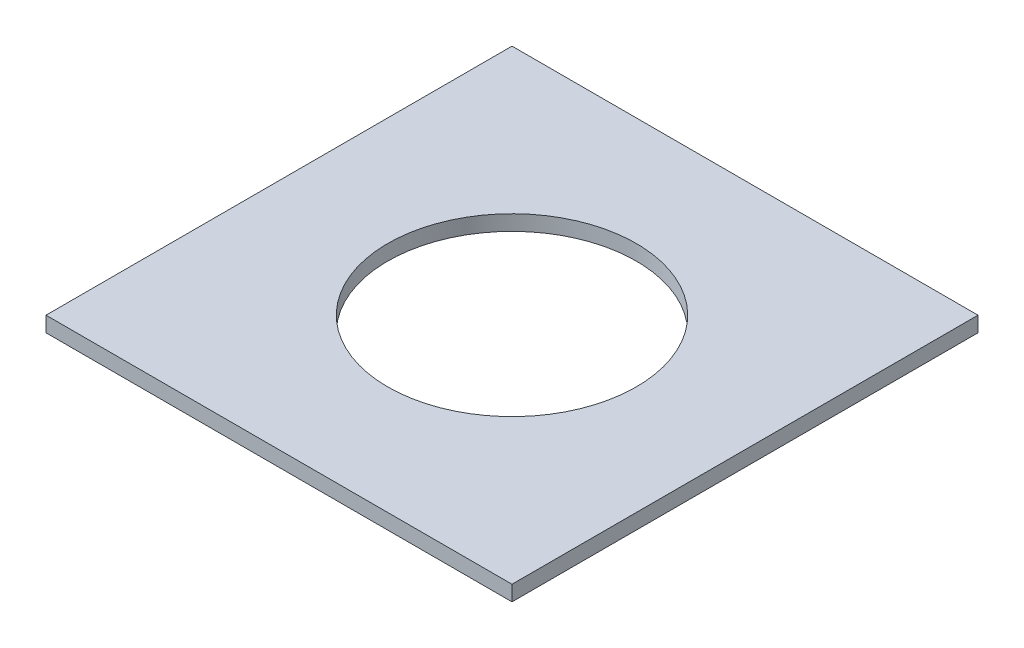
SolidWorks part; units mm, degrees
material "MDF"
ref_plane "Front Plane" through (0, 0, 0) normal (0, 0, 1) x (1, 0, 0)
ref_plane "Top Plane" through (0, 0, 0) normal (0, 1, 0) x (1, 0, 0)
ref_plane "Right Plane" through (0, 0, 0) normal (1, 0, 0) x (0, 0, -1)
sketch "Sketch1" plane through (0, 0, 0) normal (0, 1, 0) x (1, 0, 0)
  line L1 (-152.4, -152.4) -> (152.4, -152.4)
  line L2 (-152.4, -152.4) -> (-152.4, 152.4)
  line L3 (-152.4, 152.4) -> (152.4, 152.4)
  line L4 (152.4, -152.4) -> (152.4, 152.4)
  line L5 (-152.4, -152.4) -> (152.4, 152.4) construction
  line L6 (-152.4, 152.4) -> (152.4, -152.4) construction
  point P0 (0, 0)
  dimension "D1" = 304.8
extrude "Boss-Extrude1" add sketch "Sketch1" along normal blind 10
sketch "Sketch5" plane through (0, 10, 0) normal (0, 1, 0) x (1, 0, 0)
  circle A0 centre (0, 0) radius 81.2764
  circle A1 centre (0, 0) radius 81.2764
extrude "Cut-Extrude4" cut sketch "Sketch5" against normal through all
